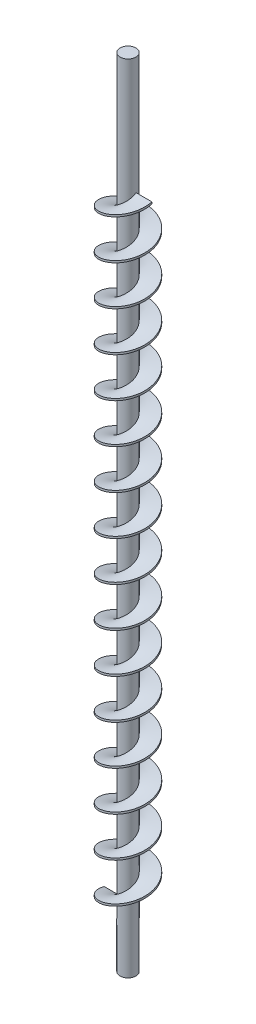
SolidWorks part; units mm, degrees
ref_plane "Front Plane" through (0, 0, 0) normal (0, 0, 1) x (1, 0, 0)
ref_plane "Top Plane" through (0, 0, 0) normal (0, 1, 0) x (1, 0, 0)
ref_plane "Right Plane" through (0, 0, 0) normal (1, 0, 0) x (0, 0, -1)
sketch "Sketch1" plane through (0, 0, 0) normal (0, 1, 0) x (1, 0, 0)
  circle A0 centre (0, 0) radius 4
  dimension "D1" = 8
extrude "Boss-Extrude1" add sketch "Sketch1" along normal blind 370
sketch "Sketch3" plane through (0, 0, 0) normal (0, -1, 0) x (1, 0, 0)
  circle A0 centre (0, 0) radius 10
curve "Helix/Spiral1" pitch 20 height 310 radius 10 centre (0, 0, 0) axis (0, 1, 0) start towards (0, 0, -1)
sketch "Sketch4" plane through (0, 0, 0) normal (0, 0, 1) x (1, 0, 0)
  line L0 (-4, 0) -> (-12, 0)
  line L1 (-12, 0) -> (-12, 1)
  line L2 (-12, 1) -> (-4, 1)
  line L3 (-4, 370) -> (-4, 0) construction
  line L4 (-4, 1) -> (-4, 0)
  dimension "D1" = 12
  dimension "D2" = 1
sweep "Sweep1" add profiles "Sketch4" path "Helix/Spiral1"
sketch "Sketch6" plane through (0, 0, 0) normal (0, -1, 0) x (1, 0, 0)
  circle A1 centre (0, 0) radius 4
  circle A2 centre (0, 0) radius 4
  dimension "D1" = 0
extrude "Boss-Extrude2" add sketch "Sketch6" along normal blind 30
